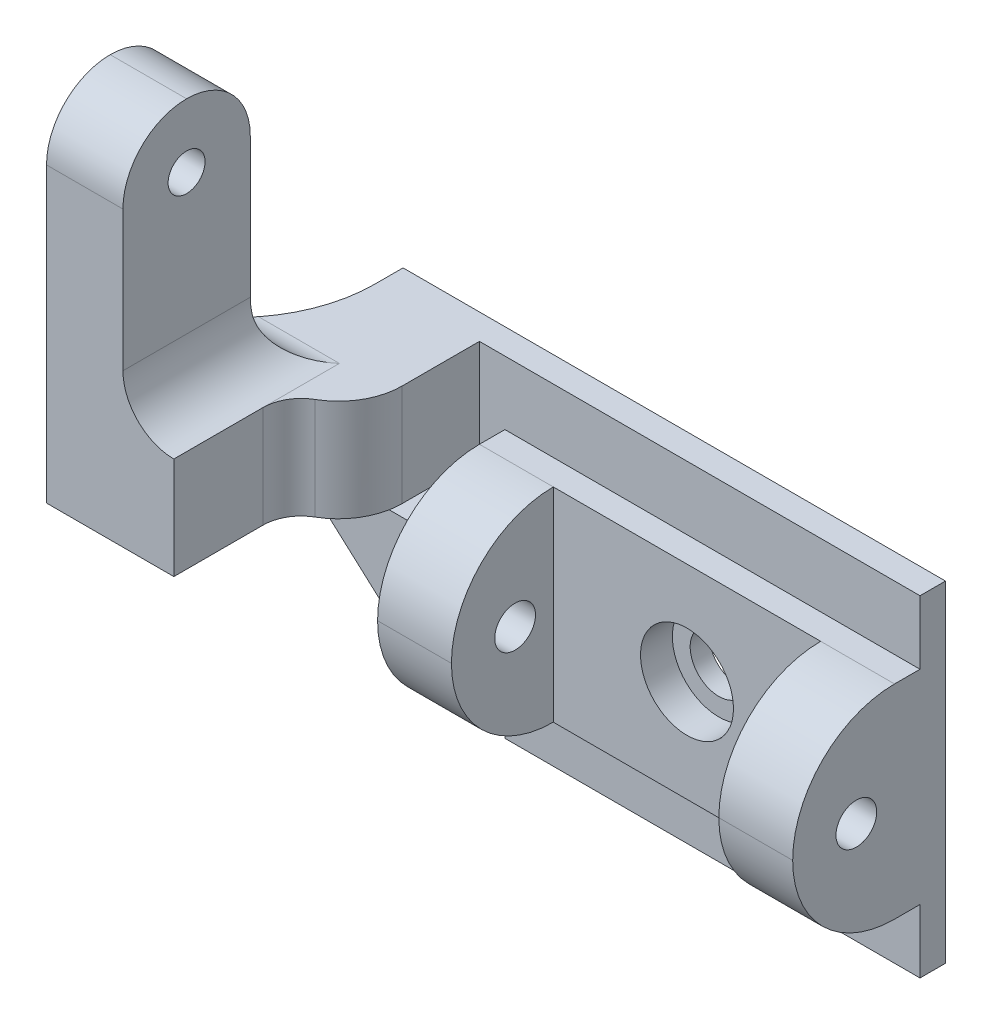
SolidWorks part; units mm, degrees
ref_plane "Front" through (0, 0, 0) normal (0, 0, 1) x (1, 0, 0)
ref_plane "Top" through (0, 0, 0) normal (0, 1, 0) x (1, 0, 0)
ref_plane "Right" through (0, 0, 0) normal (1, 0, 0) x (0, 0, -1)
sketch "Sketch1" plane through (0, 0, 0) normal (0, 0, 1) x (1, 0, 0)
  line L1 (0, 0) -> (-32.6, 0)
  line L2 (0, 0) -> (0, 26)
  line L3 (0, 26) -> (-32.6, 26)
  line L4 (-32.6, 0) -> (-32.6, 26)
  dimension "D1" = 32.6
  dimension "D2" = 26
extrude "Boss-Extrude1" add sketch "Sketch1" along normal blind 4
sketch "Sketch2" plane through (0, 0, 4) normal (0, 0, 1) x (1, 0, 0)
  line L0 (0, 26) -> (-32.6, 26) construction
  line L1 (0, 0) -> (0, 26) construction
  circle A0 centre (-16.3, 13) radius 3.65
  dimension "D1" = 7.3
  dimension "D2" = 13
  dimension "D3" = 16.3
extrude "Cut-Extrude1" cut sketch "Sketch2" against normal blind 2.5
sketch "Sketch3" plane through (0, 0, 1.5) normal (0, 0, 1) x (1, 0, 0)
  circle A0 centre (-16.3, 13) radius 2.25
  dimension "D1" = 4.5
extrude "Cut-Extrude2" cut sketch "Sketch3" against normal through all
sketch "Sketch4" plane through (0, 0, 4) normal (0, 0, 1) x (1, 0, 0)
  line L0 (-32.6, 0) -> (0, 0) construction
  line L1 (0, 26) -> (-5.8, 26)
  line L2 (0, 26) -> (0, 0)
  line L3 (0, 0) -> (-5.8, 0)
  line L4 (-5.8, 26) -> (-5.8, 0)
  line L6 (-32.6, 26) -> (-26.8, 26)
  line L7 (-32.6, 26) -> (-32.6, 0)
  line L8 (-32.6, 0) -> (-26.8, 0)
  line L9 (-26.8, 26) -> (-26.8, 0)
  dimension "D1" = 5.8
  dimension "D2" = 5.8
extrude "Boss-Extrude2" add sketch "Sketch4" along normal blind 8
sketch "Sketch5" plane through (0, 0, 0) normal (1, 0, 0) x (0, 0, -1)
  line L0 (-12, 0) -> (-12, 26) construction
  line L1 (-12, 0) -> (0, 0) construction
  circle A0 centre (-7, 13) radius 1.6
  dimension "D1" = 3.2
  dimension "D2" = 5
  dimension "D3" = 13
extrude "Cut-Extrude3" cut sketch "Sketch5" against normal through all
sketch "Sketch6" plane through (0, 0, 4) normal (0, 0, 1) x (1, 0, 0)
  line L1 (-26.8, 26) -> (-5.8, 26)
  line L2 (-26.8, 26) -> (-26.8, 21)
  line L3 (-26.8, 21) -> (-5.8, 21)
  line L4 (-5.8, 26) -> (-5.8, 21)
  line L5 (-26.8, 0) -> (-5.8, 0)
  line L6 (-26.8, 0) -> (-26.8, 5)
  line L7 (-26.8, 5) -> (-5.8, 5)
  line L8 (-5.8, 0) -> (-5.8, 5)
  dimension "D1" = 5
  dimension "D2" = 5
extrude "Boss-Extrude3" add sketch "Sketch6" along normal blind 2
sketch "Sketch7" plane through (-32.6, 0, 0) normal (-1, 0, 0) x (0, 0, 1)
  line L1 (12, 26) -> (2, 26)
  line L2 (12, 26) -> (12, 21)
  line L3 (12, 21) -> (2, 21)
  line L4 (2, 26) -> (2, 21)
  line L5 (12, 0) -> (2, 0)
  line L6 (12, 0) -> (12, 5)
  line L7 (12, 5) -> (2, 5)
  line L8 (2, 0) -> (2, 5)
  dimension "D1" = 10
  dimension "D2" = 10
  dimension "D3" = 5
  dimension "D4" = 5
extrude "Cut-Extrude4" cut sketch "Sketch7" against normal through all
sketch "Sketch12" plane through (-32.6, 0, 0) normal (-1, 0, 0) x (0, 0, 1)
  line L0 (0, 26) -> (0, 0) construction
  line L1 (2, 26) -> (0, 26)
  line L2 (2, 26) -> (2, 18)
  line L3 (2, 18) -> (0, 18)
  line L4 (0, 26) -> (0, 18)
  dimension "D1" = 8
extrude "Boss-Extrude8" add sketch "Sketch12" along normal blind 10
sketch "Sketch13" plane through (0, 0, 2) normal (0, 0, 1) x (1, 0, 0)
  line L0 (0, 26) -> (-42.6, 26) construction
  line L1 (-42.6, 18) -> (-34.6, 18)
  line L2 (-42.6, 18) -> (-42.6, 26)
  line L3 (-42.6, 26) -> (-34.6, 26)
  line L4 (-34.6, 18) -> (-34.6, 26)
  dimension "D1" = 8
extrude "Boss-Extrude9" add sketch "Sketch13" along normal blind 10
sketch "Sketch14" plane through (0, 0, 12) normal (0, 0, 1) x (1, 0, 0)
  line L0 (-42.6, 18) -> (-34.6, 18) construction
  line L1 (-38.6, 18) -> (-48.6, 18)
  line L2 (-38.6, 18) -> (-38.6, 26)
  line L3 (-38.6, 26) -> (-48.6, 26)
  line L4 (-48.6, 18) -> (-48.6, 26)
  dimension "D1" = 8
  dimension "D2" = 10
extrude "Boss-Extrude10" add sketch "Sketch14" along normal blind 10
sketch "Sketch15" plane through (0, 26, 0) normal (0, 1, 0) x (1, 0, 0)
  line L1 (-48.6, -22) -> (-42.6, -22)
  line L2 (-48.6, -22) -> (-48.6, -12)
  line L3 (-48.6, -12) -> (-42.6, -12)
  line L4 (-42.6, -22) -> (-42.6, -12)
  dimension "D1" = 10
  dimension "D2" = 6
extrude "Boss-Extrude11" add sketch "Sketch15" along normal blind 20
fillet "Fillet10" radius 11 1 edges at (-42.6, 22, 12)
fillet "Fillet11" radius 3 1 edges at (-38.6, 22, 12)
fillet "Fillet12" radius 5 1 edges at (-34.6, 22, 12)
fillet "Fillet14" radius 4 1 edges at (-42.6, 26, 17)
fillet "Fillet15" radius 3 1 edges at (-43.6, 26, 12)
sketch "Sketch16" plane through (0, 0, 0) normal (0, 0, -1) x (-1, 0, 0)
  line L0 (42.6, 18) -> (32.6, 18)
  line L1 (32.6, 18) -> (32.6, 9)
  line L2 (32.6, 18) -> (32.6, 0) construction
  line L3 (32.6, 9) -> (42.6, 18)
  dimension "D1" = 9
extrude "Boss-Extrude12" add sketch "Sketch16" against normal blind 9
fillet "Fillet17" radius 3 1 edges at (-32.6, 9, 4.5)
sketch "Sketch17" plane through (-48.6, 0, 0) normal (-1, 0, 0) x (0, 0, 1)
  line L0 (22, 46) -> (22, 18) construction
  line L1 (12, 46) -> (22, 46) construction
  circle A0 centre (17, 41) radius 1.45
  dimension "D1" = 2.9
  dimension "D2" = 5
  dimension "D3" = 5
extrude "Cut-Extrude5" cut sketch "Sketch17" against normal through all
fillet "Fillet19" radius 5 2 edges at (-45.6, 46, 12) (-45.6, 46, 22)
fillet "Fillet1" radius 8 4 edges at (-2.9, 5, 12) (-2.9, 21, 12) (-29.7, 5, 12) (-29.7, 21, 12)
